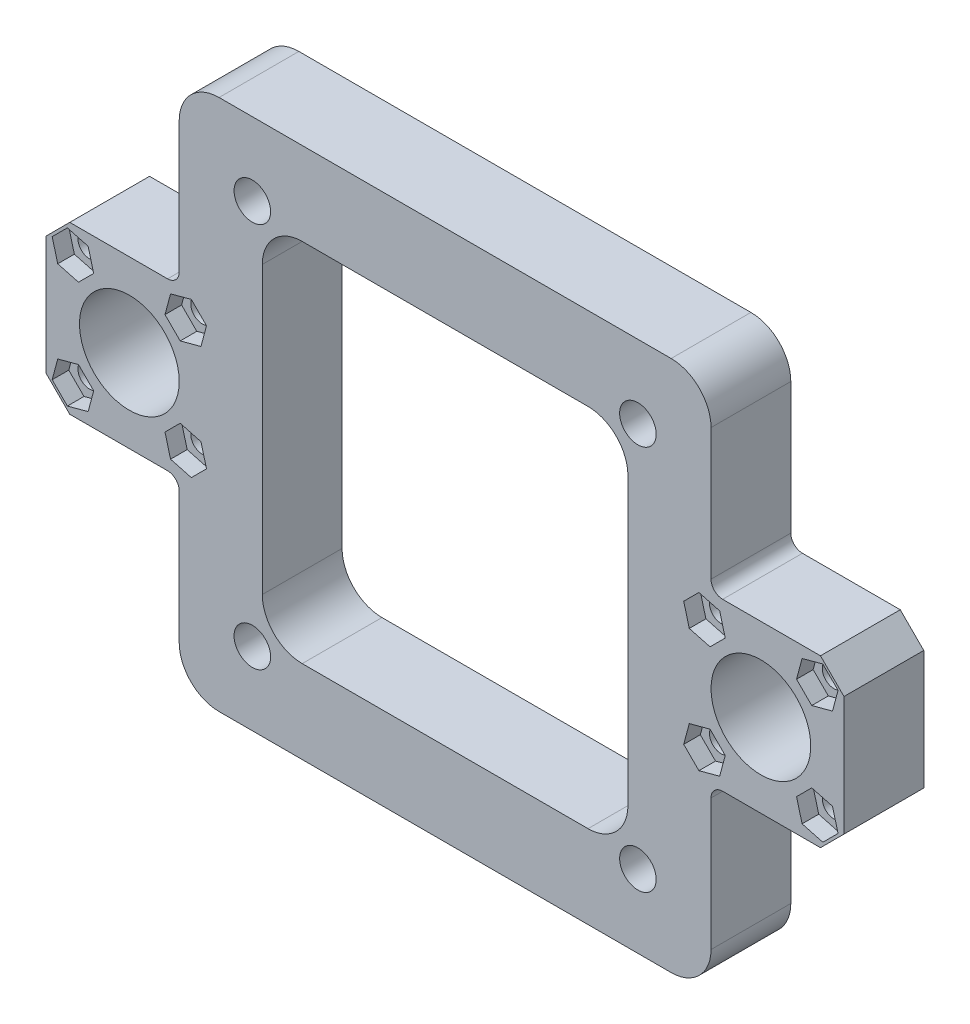
SolidWorks part; units mm, degrees
ref_plane "Front Plane" through (0, 0, 0) normal (0, 0, 1) x (1, 0, 0)
ref_plane "Top Plane" through (0, 0, 0) normal (0, 1, 0) x (1, 0, 0)
ref_plane "Right Plane" through (0, 0, 0) normal (1, 0, 0) x (0, 0, -1)
sketch "Sketch1" plane through (0, 0, 0) normal (0, 0, 1) x (1, 0, 0)
  line L0 (-47.5, 0) -> (47.5, 0) construction
  line L1 (0, 0) -> (0, 17.3262) construction
  line L2 (-56.4645, 12.5) -> (-41.75, 12.5)
  line L3 (-40, 14.25) -> (-40, 34)
  line L12 (-56.4645, 12.5) -> (-60, 8.9645)
  line L13 (-60, 8.9645) -> (-60, -8.9645)
  line L14 (34, 40) -> (-34, 40)
  line L15 (60, 8.9645) -> (60, -8.9645)
  line L16 (56.4645, 12.5) -> (60, 8.9645)
  line L17 (56.4645, 12.5) -> (41.75, 12.5)
  line L18 (40, 14.25) -> (40, 34)
  line L19 (-56.4645, -12.5) -> (-60, -8.9645)
  line L20 (-56.4645, -12.5) -> (-41.75, -12.5)
  line L21 (-40, -14.25) -> (-40, -34)
  line L22 (34, -40) -> (-34, -40)
  line L23 (40, -14.25) -> (40, -34)
  line L24 (56.4645, -12.5) -> (41.75, -12.5)
  line L25 (56.4645, -12.5) -> (60, -8.9645)
  line L26 (-55.9853, 8.4853) -> (-39.0147, -8.4853) construction
  line L27 (-55.9853, -8.4853) -> (-39.0147, 8.4853) construction
  circle A0 centre (-47.5, 0) radius 7.5
  arc A12 (-41.75, 12.5) -> (-40, 14.25) centre (-41.75, 14.25) ccw
  arc A13 (-40, 34) -> (-34, 40) centre (-34, 34) cw
  arc A14 (41.75, 12.5) -> (40, 14.25) centre (41.75, 14.25) cw
  arc A15 (40, 34) -> (34, 40) centre (34, 34) ccw
  arc A16 (-41.75, -12.5) -> (-40, -14.25) centre (-41.75, -14.25) cw
  arc A17 (-40, -34) -> (-34, -40) centre (-34, -34) ccw
  arc A18 (40, -34) -> (34, -40) centre (34, -34) cw
  arc A19 (41.75, -12.5) -> (40, -14.25) centre (41.75, -14.25) ccw
  circle A20 centre (47.5, 0) radius 7.5
  circle A21 centre (-55.9853, 8.4853) radius 1.75
  circle A22 centre (-39.0147, -8.4853) radius 1.75
  circle A23 centre (-39.0147, 8.4853) radius 1.75
  circle A24 centre (-55.9853, -8.4853) radius 1.75
  circle A25 centre (39.0147, -8.4853) radius 1.75
  circle A26 centre (55.9853, -8.4853) radius 1.75
  circle A27 centre (55.9853, 8.4853) radius 1.75
  circle A28 centre (39.0147, 8.4853) radius 1.75
  circle A29 centre (-29, 29) radius 2.75
  circle A33 centre (29, 29) radius 2.75
  circle A34 centre (29, -29) radius 2.75
  circle A35 centre (-29, -29) radius 2.75
  point P28 (0, 40)
  point P29 (-60, 0)
  point P44 (60, 0)
  dimension "D2" = 15
  dimension "D3" = 25
  dimension "D6" = 1.75
  dimension "D11" = 3.5
  dimension "D13" = 6
  dimension "D15" = 5.5
  dimension "D1" = 95
  dimension "D4" = 120
  dimension "D5" = 40
  dimension "D7" = 135
  dimension "D8" = 80
  dimension "D9" = 5
  dimension "D10" = 24
  dimension "D12" = 135
  dimension "D14" = 58
  dimension "D16" = 58
extrude "Boss-Extrude1" add sketch "Sketch1" along normal blind 12
sketch "Sketch2" plane through (0, 0, 12) normal (0, 0, 1) x (1, 0, 0)
  line L0 (-21.5, 21.5) -> (21.5, -21.5) construction
  line L1 (-21.5, 27.5) -> (21.5, 27.5)
  line L2 (-27.5, 21.5) -> (-27.5, -21.5)
  line L3 (-21.5, -27.5) -> (21.5, -27.5)
  line L4 (27.5, 21.5) -> (27.5, -21.5)
  arc A0 (-27.5, -21.5) -> (-21.5, -27.5) centre (-21.5, -21.5) ccw
  arc A1 (21.5, -27.5) -> (27.5, -21.5) centre (21.5, -21.5) ccw
  arc A2 (27.5, 21.5) -> (21.5, 27.5) centre (21.5, 21.5) ccw
  arc A3 (-21.5, 27.5) -> (-27.5, 21.5) centre (-21.5, 21.5) ccw
  dimension "D1" = 6
  dimension "D2" = 55
extrude "Cut-Extrude1" cut sketch "Sketch2" against normal through all both and the other way through all
sketch "Sketch3" plane through (0, 0, 12) normal (0, 0, 1) x (1, 0, 0)
  line L0 (-56.4645, 12.5) -> (-60, 8.9645) construction
  line L1 (-55.1485, 5.3623) -> (-52.8623, 7.6485)
  line L2 (-52.8623, 7.6485) -> (-53.6991, 10.7715)
  line L3 (-53.6991, 10.7715) -> (-56.8221, 11.6083)
  line L4 (-56.8221, 11.6083) -> (-59.1083, 9.3221)
  line L5 (-59.1083, 9.3221) -> (-58.2715, 6.1991)
  line L6 (-58.2715, 6.1991) -> (-55.1485, 5.3623)
  line L7 (-42.1377, 7.6485) -> (-39.8515, 5.3623)
  line L8 (-39.8515, 5.3623) -> (-36.7285, 6.1991)
  line L9 (-36.7285, 6.1991) -> (-35.8917, 9.3221)
  line L10 (-35.8917, 9.3221) -> (-38.1779, 11.6083)
  line L11 (-38.1779, 11.6083) -> (-41.3009, 10.7715)
  line L12 (-41.3009, 10.7715) -> (-42.1377, 7.6485)
  line L13 (-39.8515, -5.3623) -> (-42.1377, -7.6485)
  line L14 (-42.1377, -7.6485) -> (-41.3009, -10.7715)
  line L15 (-41.3009, -10.7715) -> (-38.1779, -11.6083)
  line L16 (-38.1779, -11.6083) -> (-35.8917, -9.3221)
  line L17 (-35.8917, -9.3221) -> (-36.7285, -6.1991)
  line L18 (-36.7285, -6.1991) -> (-39.8515, -5.3623)
  line L19 (-52.8623, -7.6485) -> (-55.1485, -5.3623)
  line L20 (-55.1485, -5.3623) -> (-58.2715, -6.1991)
  line L21 (-58.2715, -6.1991) -> (-59.1083, -9.3221)
  line L22 (-59.1083, -9.3221) -> (-56.8221, -11.6083)
  line L23 (-56.8221, -11.6083) -> (-53.6991, -10.7715)
  line L24 (-53.6991, -10.7715) -> (-52.8623, -7.6485)
  circle A0 centre (-55.9853, 8.4853) radius 2.8 construction
  circle A1 centre (-55.9853, 8.4853) radius 1.75 construction
  circle A2 centre (-47.5, 0) radius 7.5 construction
  circle A3 centre (-47.5, 0) radius 7.5 construction
  circle A4 centre (-39.0147, 8.4853) radius 2.8 construction
  circle A5 centre (-39.0147, -8.4853) radius 2.8 construction
  circle A6 centre (-55.9853, -8.4853) radius 2.8 construction
  point P1 (-47.5, 0)
  point P13 (-40.4943, 8.4853)
  point P17 (0, 0)
  point P42 (-47.5, 0)
  dimension "D1" = 5.6
  dimension "D2" = 4
extrude "Cut-Extrude2" cut sketch "Sketch3" against normal blind 2.5
mirror "Mirror1" about plane through (0, 0, 0) normal (1, 0, 0) of "Cut-Extrude2"
